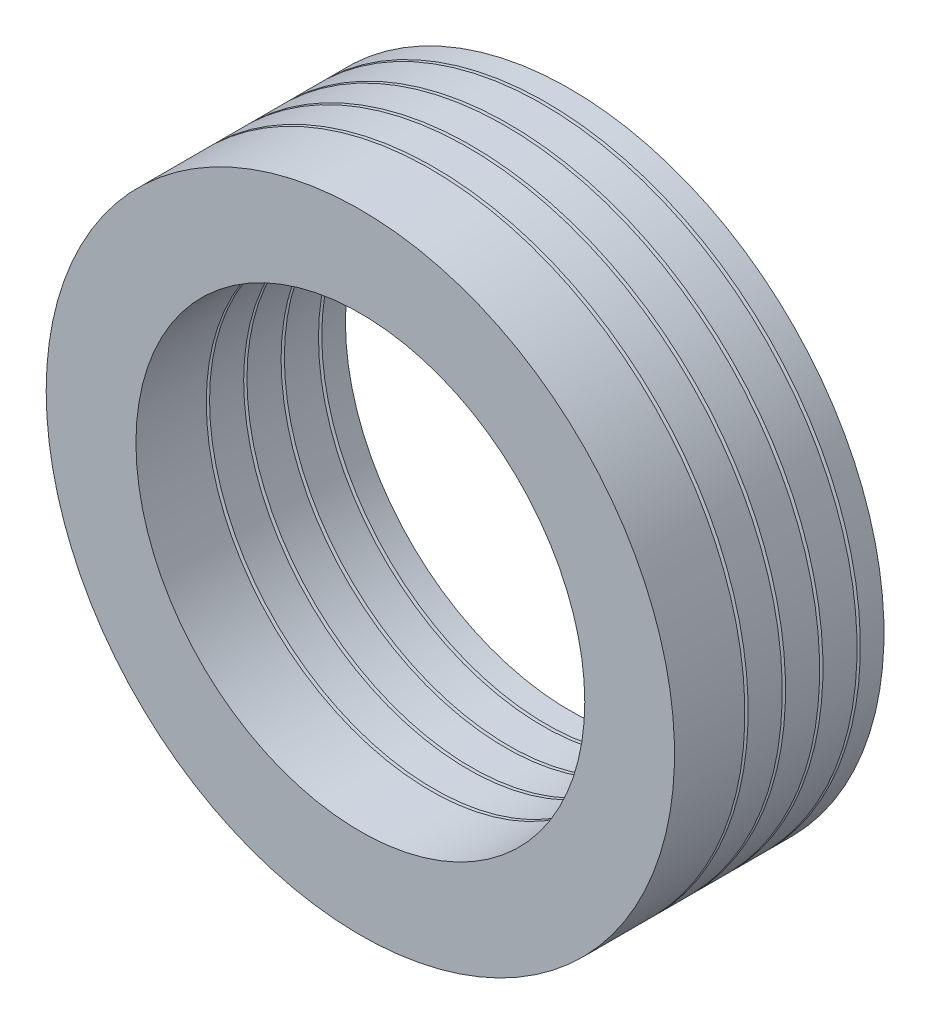
SolidWorks part; units mm, degrees
material "EPDM 60 Durometer"
ref_plane "Front" through (0, 0, 0) normal (0, 0, 1) x (1, 0, 0)
ref_plane "Top" through (0, 0, 0) normal (0, 1, 0) x (1, 0, 0)
ref_plane "Right" through (0, 0, 0) normal (1, 0, 0) x (0, 0, -1)
ref_axis "Axis1" through (-84.4107, 0, 0) along (1, 0, 0)
ref_axis "Axis2" through (0, 64.3378, 0) along (0, -1, 0)
ref_axis "Axis3" through (0, 0, -102.329) along (0, 0, 1)
sketch "Sketch1" plane through (0, 0, 0) normal (0, 0, 1) x (1, 0, 0)
  circle A0 centre (0, 0) radius 15
  dimension "D1" = 30
sketch "Sketch4" plane through (0, 0, 0) normal (0, 1, 0) x (1, 0, 0)
  line L0 (-18, 14.0048) -> (-18, 0.0048) construction
  line L1 (-15, 0.0048) -> (-21, 0.0048)
  line L2 (-15, 0.0048) -> (-15, 4.7048)
  line L3 (-15, 14.0048) -> (-17.5, 14.0048)
  line L4 (-21, 0.0048) -> (-21, 4.7048)
  line L5 (-21, 12.4248) -> (-18, 10.9803)
  line L6 (-18, 10.9803) -> (-15, 12.4248)
  line L7 (-17.5, 11.0011) -> (-15, 12.2048)
  line L8 (-21, 12.2048) -> (-18.5, 11.0011)
  line L9 (-21, 9.9248) -> (-18, 8.4803)
  line L10 (-18, 8.4803) -> (-15, 9.9248)
  line L11 (-21, 9.7048) -> (-18.5, 8.5011)
  line L12 (-17.5, 8.5011) -> (-15, 9.7048)
  line L13 (-21, 7.4248) -> (-18, 5.9803)
  line L14 (-18, 5.9803) -> (-15, 7.4248)
  line L15 (-21, 7.2048) -> (-18.5, 6.0011)
  line L16 (-17.5, 6.0011) -> (-15, 7.2048)
  line L17 (-21, 4.9248) -> (-18, 3.4803)
  line L18 (-18, 3.4803) -> (-15, 4.9248)
  line L19 (-21, 4.7048) -> (-18.5, 3.5011)
  line L20 (-17.5, 3.5011) -> (-15, 4.7048)
  line L21 (-18.5, 11.0011) -> (-18.5, 10.6068)
  line L23 (-18.5, 14.0048) -> (-18.5, 13.6148)
  line L24 (-18.5, 13.6148) -> (-17.5, 13.6148)
  line L25 (-17.5, 14.0048) -> (-17.5, 13.6148)
  line L26 (-18.5, 10.6068) -> (-17.5, 10.6068)
  line L27 (-17.5, 10.6068) -> (-17.5, 11.0011)
  line L28 (-18.5, 8.5011) -> (-18.5, 8.1068)
  line L29 (-18.5, 8.1068) -> (-17.5, 8.1068)
  line L30 (-17.5, 8.1068) -> (-17.5, 8.5011)
  line L31 (-18.5, 6.0011) -> (-18.5, 5.6068)
  line L32 (-18.5, 5.6068) -> (-17.5, 5.6068)
  line L33 (-17.5, 5.6068) -> (-17.5, 6.0011)
  line L34 (-18.5, 3.5011) -> (-18.5, 3.1068)
  line L35 (-18.5, 3.1068) -> (-17.5, 3.1068)
  line L36 (-17.5, 3.1068) -> (-17.5, 3.5011)
  line L37 (-18.5, 14.0048) -> (-21, 14.0048)
  line L38 (-21, 12.4248) -> (-21, 14.0048)
  line L39 (-15, 12.4248) -> (-15, 14.0048)
  line L40 (-21, 9.9248) -> (-21, 12.2048)
  line L41 (-15, 9.9248) -> (-15, 12.2048)
  line L42 (-21, 7.4248) -> (-21, 9.7048)
  line L43 (-15, 7.4248) -> (-15, 9.7048)
  line L44 (-15, 4.9248) -> (-15, 7.2048)
  line L45 (-21, 4.9248) -> (-21, 7.2048)
  dimension "D1" = 15
  dimension "D2" = 21
  dimension "D3" = 14
  dimension "D4" = 25.71
  dimension "D5" = 1.58
  dimension "D7" = 1
  dimension "D8" = 0.5
  dimension "D9" = 0.39
revolve "Revolve1" add sketch "Sketch4" angle 360 about axis through (0, 0, -102.329) along (0, 0, 1)
